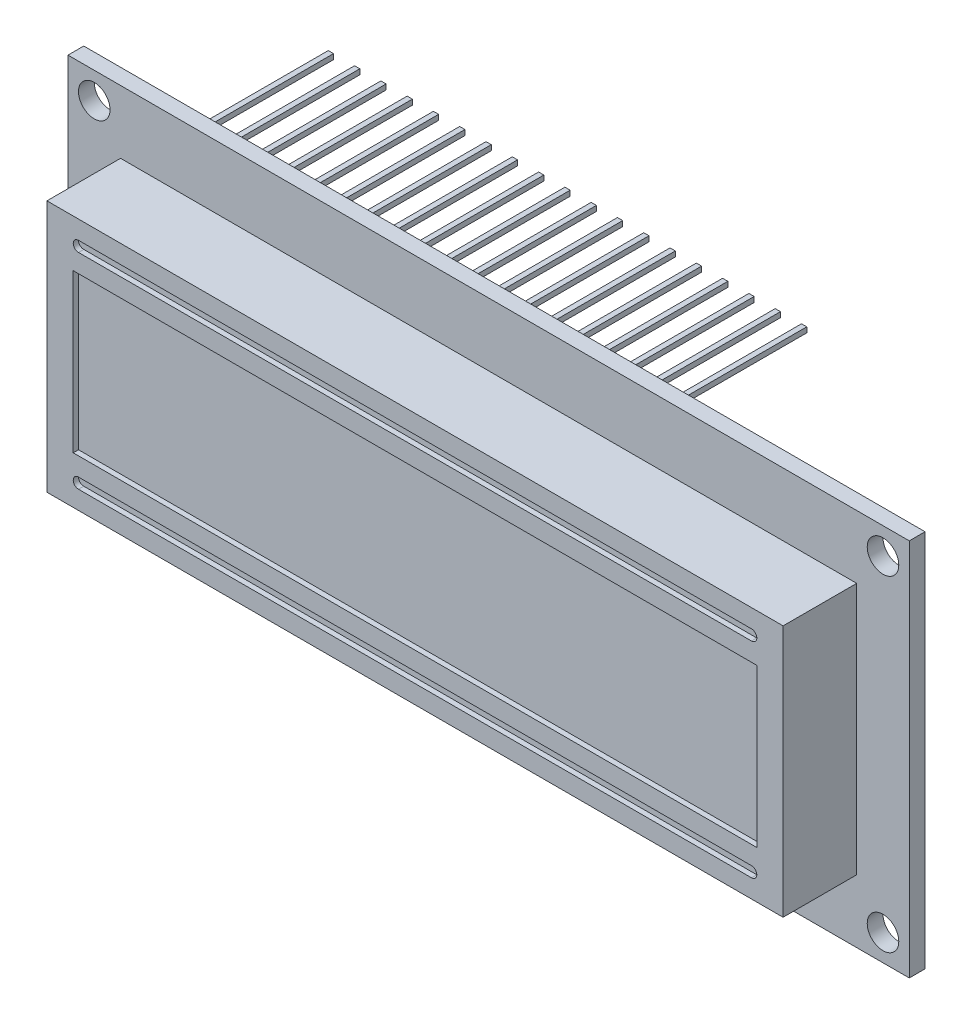
SolidWorks part; units mm, degrees
ref_plane "Front Plane" through (0, 0, 0) normal (0, 0, 1) x (1, 0, 0)
ref_plane "Top Plane" through (0, 0, 0) normal (0, 1, 0) x (1, 0, 0)
ref_plane "Right Plane" through (0, 0, 0) normal (1, 0, 0) x (0, 0, -1)
sketch "Sketch1" plane through (0, 0, 0) normal (0, 0, 1) x (1, 0, 0)
  line L1 (40, -18) -> (-40, -18)
  line L2 (40, -18) -> (40, 18)
  line L3 (40, 18) -> (-40, 18)
  line L4 (-40, -18) -> (-40, 18)
  line L5 (40, -18) -> (-40, 18) construction
  line L6 (40, 18) -> (-40, -18) construction
  point P0 (0, 0)
  dimension "D1" = 80
  dimension "D2" = 36
base flange "Base-Flange1" sketch "Sketch1" thickness 1.5 reverse thickness direction no parameters "D1"=1.2
sketch "Sketch6" plane through (0, 0, 0) normal (0, 0, 1) x (1, 0, 0)
  line L1 (35, -12) -> (-35, -12)
  line L2 (35, -12) -> (35, 12)
  line L3 (35, 12) -> (-35, 12)
  line L4 (-35, -12) -> (-35, 12)
  line L5 (35, -12) -> (-35, 12) construction
  line L6 (35, 12) -> (-35, -12) construction
  point P0 (0, 0)
  dimension "D1" = 24
  dimension "D2" = 70
extrude "Boss-Extrude1" add sketch "Sketch6" along normal blind 7
sketch "Sketch7" plane through (0, 0, 7) normal (0, 0, 1) x (1, 0, 0)
  line L1 (32.5, -7.5) -> (-32.5, -7.5)
  line L2 (32.5, -7.5) -> (32.5, 7.5)
  line L3 (32.5, 7.5) -> (-32.5, 7.5)
  line L4 (-32.5, -7.5) -> (-32.5, 7.5)
  line L5 (32.5, -7.5) -> (-32.5, 7.5) construction
  line L6 (32.5, 7.5) -> (-32.5, -7.5) construction
  point P0 (0, 0)
  dimension "D1" = 15
  dimension "D2" = 65
extrude "Cut-Extrude1" cut sketch "Sketch7" against normal blind 0.5 normal cut yes
sketch "Sketch8" plane through (0, 0, 7) normal (0, 0, 1) x (1, 0, 0)
  line L0 (32, 9.75) -> (-32, 9.75) construction
  line L1 (32, 9.25) -> (-32, 9.25)
  line L2 (32, 10.25) -> (-32, 10.25)
  line L3 (35, 12) -> (-35, 12) construction
  line L4 (-32.5, 0) -> (32.5, 0) construction
  line L5 (-32.5, 7.5) -> (-32.5, -7.5) construction
  line L6 (32.5, -7.5) -> (32.5, 7.5) construction
  line L7 (32, -9.75) -> (-32, -9.75) construction
  line L8 (32, -9.25) -> (-32, -9.25)
  line L9 (32, -10.25) -> (-32, -10.25)
  arc A0 (32, 9.25) -> (32, 10.25) centre (32, 9.75) ccw
  arc A1 (-32, 10.25) -> (-32, 9.25) centre (-32, 9.75) ccw
  arc A2 (32, -9.25) -> (32, -10.25) centre (32, -9.75) cw
  arc A3 (-32, -10.25) -> (-32, -9.25) centre (-32, -9.75) cw
  point P2 (0, 9.75)
  point P18 (0, -9.75)
  dimension "D1" = 64
  dimension "D2" = 1
  dimension "D3" = 2.25
extrude "Cut-Extrude2" cut sketch "Sketch8" against normal blind 0.5 normal cut yes
sketch "Sketch9" plane through (0, 0, -1.5) normal (0, 0, -1) x (-1, 0, 0)
  line L1 (37.5, -15.5) -> (-37.5, -15.5) construction
  line L2 (37.5, -15.5) -> (37.5, 15.5) construction
  line L3 (37.5, 15.5) -> (-37.5, 15.5) construction
  line L4 (-37.5, -15.5) -> (-37.5, 15.5) construction
  line L5 (37.5, -15.5) -> (-37.5, 15.5) construction
  line L6 (37.5, 15.5) -> (-37.5, -15.5) construction
  circle A0 centre (-37.5, 15.5) radius 1.5
  circle A1 centre (-37.5, -15.5) radius 1.5
  circle A2 centre (37.5, 15.5) radius 1.5
  circle A3 centre (37.5, -15.5) radius 1.5
  point P0 (0, 0)
  dimension "D3" = 3
  dimension "D1" = 75
  dimension "D2" = 31
extrude "Cut-Extrude3" cut sketch "Sketch9" against normal up to next normal cut yes
sketch "Sketch10" plane through (0, 0, -1.5) normal (0, 0, -1) x (-1, 0, 0)
  line L0 (40, 18) -> (40, -18) construction
  line L1 (32, 14) -> (-16, 14)
  line L2 (32, 14) -> (32, 16)
  line L3 (32, 16) -> (-16, 16)
  line L4 (-16, 14) -> (-16, 16)
  line L5 (-40, 18) -> (40, 18) construction
  dimension "D1" = 2
  dimension "D2" = 8
  dimension "D3" = 48
  dimension "D4" = 2
extrude "Boss-Extrude2" add sketch "Sketch10" along normal blind 2
sketch "Sketch11" plane through (0, 0, -3.5) normal (0, 0, -1) x (-1, 0, 0)
  line L0 (32, 14) -> (32, 16) construction
  line L1 (30.25, 14.75) -> (30.75, 14.75)
  line L2 (30.25, 14.75) -> (30.25, 15.25)
  line L3 (30.25, 15.25) -> (30.75, 15.25)
  line L4 (30.75, 14.75) -> (30.75, 15.25)
  line L5 (30.25, 14.75) -> (30.75, 15.25) construction
  line L6 (30.25, 15.25) -> (30.75, 14.75) construction
  point P0 (30.5, 15)
  point P7 (32, 15)
  dimension "D1" = 0.5
  dimension "D2" = 0.5
  dimension "D3" = 1.5
extrude "Boss-Extrude3" add sketch "Sketch11" along normal blind 12
pattern_linear "LPattern1" count 19 spacing 2.5 along (1, 0, 0) of "Boss-Extrude3"
sketch "Bend-Lines1" plane through (0, 0, 0) normal (0, 1, 0) x (1, 0, 0)
sketch "Bounding-Box1" plane through (0, 0, 0) normal (0, 1, 0) x (1, 0, 0)
sheet metal parameters "Sheet-Metal1" thickness 1.5 parameters "D1"=1.2
flat pattern "Flat-Pattern1" [suppressed]
sketch "Bend-Lines2" plane through (0, 0, 0) normal (0, 1, 0) x (1, 0, 0)
sketch "Bounding-Box2" [suppressed] plane through (0, 0, 0) normal (0, 1, 0) x (1, 0, 0)
sheet metal parameters "Sheet-Metal2" thickness 1.5 parameters "D1"=1.2
flat pattern "Flat-Pattern1"
sketch "Bend-Lines2" plane through (0, 0, 0) normal (0, 1, 0) x (1, 0, 0)
sketch "Bounding-Box2" [suppressed] plane through (0, 0, 0) normal (0, 1, 0) x (1, 0, 0)
sheet metal parameters "Sheet-Metal3" thickness 1.5 parameters "D1"=1.2
flat pattern "Flat-Pattern1"
sketch "Bend-Lines2" plane through (0, 0, 0) normal (0, 1, 0) x (1, 0, 0)
sketch "Bounding-Box2" [suppressed] plane through (0, 0, 0) normal (0, 1, 0) x (1, 0, 0)
sheet metal parameters "Sheet-Metal4" thickness 1.5 parameters "D1"=1.2
flat pattern "Flat-Pattern1"
sketch "Bend-Lines2" plane through (0, 0, 0) normal (0, 1, 0) x (1, 0, 0)
sketch "Bounding-Box2" [suppressed] plane through (0, 0, 0) normal (0, 1, 0) x (1, 0, 0)
sheet metal parameters "Sheet-Metal5" thickness 1.5 parameters "D1"=1.2
flat pattern "Flat-Pattern1"
sketch "Bend-Lines2" plane through (0, 0, 0) normal (0, 1, 0) x (1, 0, 0)
sketch "Bounding-Box2" [suppressed] plane through (0, 0, 0) normal (0, 1, 0) x (1, 0, 0)
sheet metal parameters "Sheet-Metal6" thickness 1.5 parameters "D1"=1.2
flat pattern "Flat-Pattern1"
sketch "Bend-Lines2" plane through (0, 0, 0) normal (0, 1, 0) x (1, 0, 0)
sketch "Bounding-Box2" [suppressed] plane through (0, 0, 0) normal (0, 1, 0) x (1, 0, 0)
sheet metal parameters "Sheet-Metal7" thickness 1.5 parameters "D1"=1.2
flat pattern "Flat-Pattern1"
sketch "Bend-Lines2" plane through (0, 0, 0) normal (0, 1, 0) x (1, 0, 0)
sketch "Bounding-Box2" [suppressed] plane through (0, 0, 0) normal (0, 1, 0) x (1, 0, 0)
sheet metal parameters "Sheet-Metal8" thickness 1.5 parameters "D1"=1.2
flat pattern "Flat-Pattern1"
sketch "Bend-Lines2" plane through (0, 0, 0) normal (0, 1, 0) x (1, 0, 0)
sketch "Bounding-Box2" [suppressed] plane through (0, 0, 0) normal (0, 1, 0) x (1, 0, 0)
